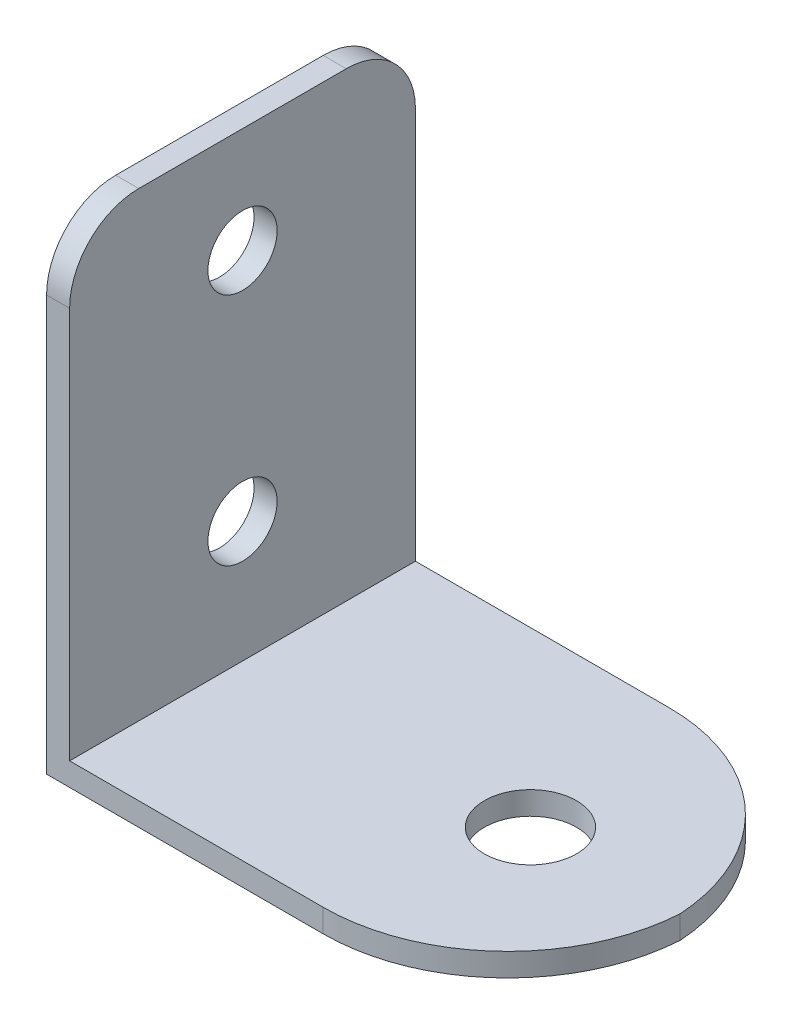
SolidWorks part; units mm, degrees
ref_plane "Front Plane" through (0, 0, 0) normal (0, 0, 1) x (1, 0, 0)
ref_plane "Top Plane" through (0, 0, 0) normal (0, 1, 0) x (1, 0, 0)
ref_plane "Right Plane" through (0, 0, 0) normal (1, 0, 0) x (0, 0, -1)
sketch "Sketch1" plane through (0, 0, 0) normal (0, 0, 1) x (1, 0, 0)
  line L0 (0, 0) -> (0, 20)
  line L1 (0, 0) -> (19, 0)
extrude "Extrude-Thin1" add sketch "Sketch1" along normal blind 15 thin thin type one direction wall 1
fillet "Fillet1" radius 8 2 edges at (19, -0.5, 0) (19, -0.5, 15)
sketch "Sketch2" plane through (-1, 0, 0) normal (-1, 0, 0) x (0, 0, 1)
  circle A0 centre (7.5, 5.2476) radius 1.5
  circle A1 centre (7.5, 15.4201) radius 1.5
extrude "Cut-Extrude1" cut sketch "Sketch2" against normal through all
fillet "Fillet2" radius 3 2 edges at (-0.5, 20, 15) (-0.5, 20, 0)
sketch "Sketch3" plane through (0, 0, 0) normal (0, 1, 0) x (1, 0, 0)
  circle A0 centre (12.4876, -7.5) radius 2
extrude "Cut-Extrude2" cut sketch "Sketch3" against normal through all
